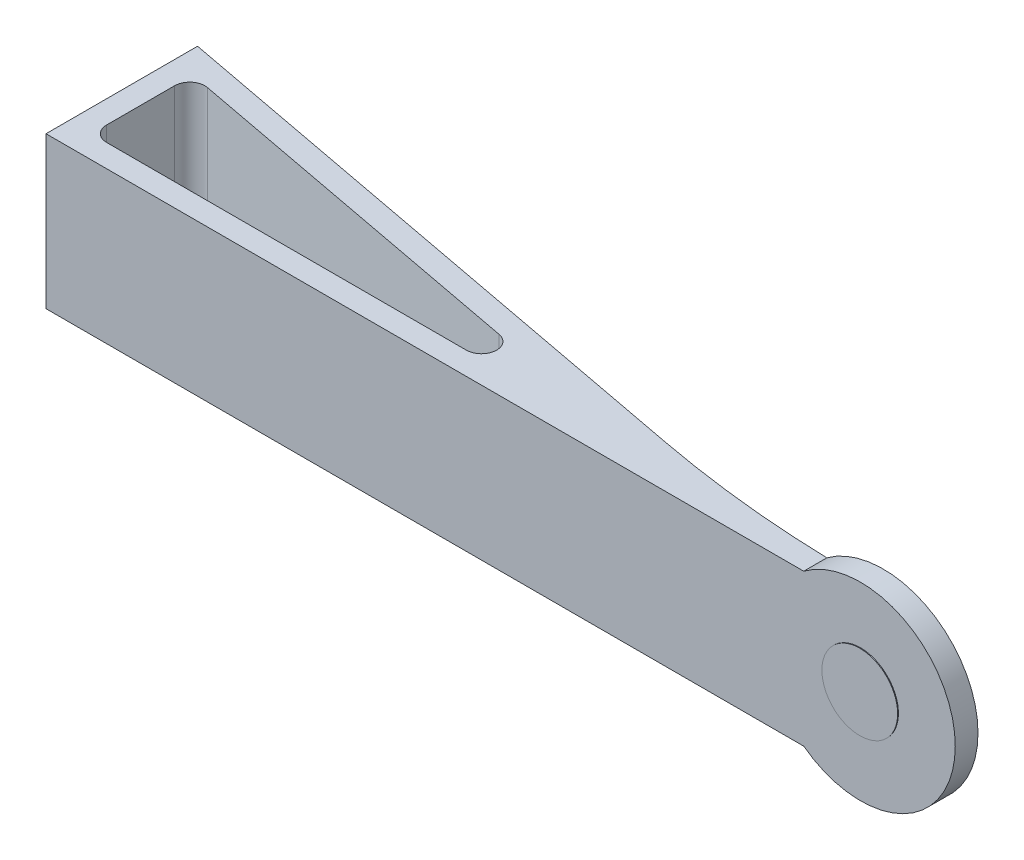
SolidWorks part; units mm, degrees
note: The reader was unsure of these and kept them because the rebuilt part matched: shared geometry of "Sketch3<2>", "Sketch3<3>".
ref_plane "Front Plane" through (0, 0, 0) normal (0, 0, 1) x (1, 0, 0)
ref_plane "Top Plane" through (0, 0, 0) normal (0, 1, 0) x (1, 0, 0)
ref_plane "Right Plane" through (0, 0, 0) normal (1, 0, 0) x (0, 0, -1)
sketch "Sketch2" plane through (0, 0, 0) normal (0, 0, 1) x (1, 0, 0)
  line L0 (0, 0) -> (0, 20)
  line L1 (0, 20) -> (90, 3)
  line L2 (90, 3) -> (115, 3)
  line L3 (115, 3) -> (115, 0)
  line L4 (115, 0) -> (0, 0)
  line L5 (73.8368, 3) -> (3, 3)
  line L6 (3, 3) -> (3, 16.3803)
  line L7 (3, 16.3803) -> (73.8368, 3)
  dimension "D1" = 3
  dimension "D2" = 20
  dimension "D3" = 3
  dimension "D4" = 3
  dimension "D5" = 90
  dimension "D6" = 115
extrude "Boss-Extrude1" add sketch "Sketch2" along normal blind 20
sketch "Sketch3" plane through (0, 3, 0) normal (0, 1, 0) x (1, 0, 0)
  line L0 (115, -10) -> (90, -10) construction
  line L1 (115, -20) -> (115, 0) construction
  line L2 (90, -20) -> (90, 0) construction
  line L3 (0, -20) -> (0, 0) construction
  circle A0 centre (107.5, -10) radius 12.5
  circle A1 centre (107.5, -10) radius 5
  dimension "D1" = 25
  dimension "D2" = 5
  dimension "D3" = 120
extrude "Boss-Extrude2" add sketch "Sketch3" against normal up to surface (3 mm away) up to face at (57.5, 0, 10)
extrude "Cut-Extrude1" cut sketch "Sketch3<2>" against normal blind 25.4 contours L0 A1 | A1 L0
sketch "Sketch3<2>" plane through (0, 3, 0) normal (0, 1, 0) x (1, 0, 0) same geometry as "Sketch3"
extrude "Boss-Extrude3" add sketch "Sketch3<3>" against normal offset from surface (3.2 mm away) 0.1 from offset 0.1 contours L0 A1 | A1 L0
sketch "Sketch3<3>" plane through (0, 3, 0) normal (0, 1, 0) x (1, 0, 0) same geometry as "Sketch3"
fillet "Fillet1" radius 150 1 edges at (90, 3, 10)
fillet "Fillet2" radius 2 3 edges at (3, 3, 10) (3, 16.3803, 10) (73.8368, 3, 10)
move or copy body "Body-Move/Copy1" bodies to move or copy 105 copy no rotation origin (0, 0, 0) rotation axis (-1, 0, 0) rotation angle 90
